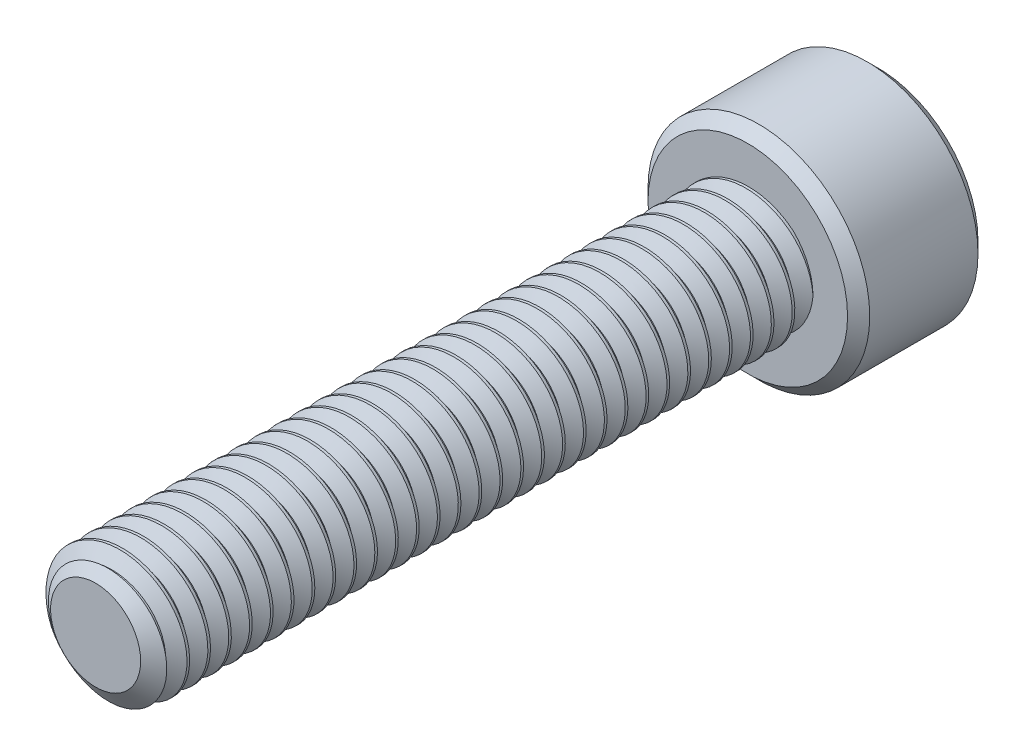
SolidWorks part; units mm, degrees
other "DetailItem1"
ref_plane "Front Plane" through (0, 0, 0) normal (0, 0, 1) x (1, 0, 0)
ref_plane "Top Plane" through (0, 0, 0) normal (0, 1, 0) x (1, 0, 0)
ref_plane "Right Plane" through (0, 0, 0) normal (1, 0, 0) x (0, 0, -1)
sketch "Sketch1" plane through (0, 0, 0) normal (0, 0, 1) x (1, 0, 0)
  circle A0 centre (0, 0) radius 2.5
  dimension "OD" = 5
extrude "Extrude1" add sketch "Sketch1" against normal blind 25
sketch "Sketch2" plane through (0, 0, 0) normal (0, 0, 1) x (1, 0, 0)
  circle A0 centre (0, 0) radius 2.5 construction
  circle A1 centre (0, 0) radius 2.5
curve "Helix/Spiral1" pitch 0.8 height 25.8 turns 32.25 parameters "pitch"=0.8
sketch "Sketch3" plane through (0, 0, 0) normal (1, 0, 0) x (0, 0, -1)
  line L0 (-0.7, 2.5) -> (-0.4, 1.9804)
  line L1 (-0.4, 1.9804) -> (-0.3, 1.9804)
  line L2 (-0.3, 1.9804) -> (0, 2.5)
  line L3 (-0.7, 2.5) -> (0, 2.5)
  line L4 (-0.35, 2.5) -> (-0.35, 1.9804) construction
  line L5 (-0.55, 2.2402) -> (-0.15, 2.2402) construction
  line L6 (0, 2.5) -> (0, -2.5) construction
  dimension "D1" = 0.1
  dimension "D2" = 0.4
  dimension "D3" = 60
sweep "Cut-Sweep1" cut profiles "Sketch3" path "Helix/Spiral1"
sketch "Sketch4" plane through (0, 0, 0) normal (1, 0, 0) x (0, 0, -1)
  line L0 (0.5417, 2.5) -> (0, 1.7264)
  line L1 (0, 1.7264) -> (0, 2.5)
  line L2 (0.5417, 2.5) -> (0, 2.5)
  line L3 (-0.7, 2.5) -> (0, 2.5) construction
  line L4 (0, 0) -> (7.0209, 0) construction
  dimension "D1" = 55
  dimension "D2" = 0.254
revolve "Cut-Revolve1" cut sketch "Sketch4" angle 360 about L4
sketch "Sketch6" plane through (0, 0, -25) normal (0, 0, -1) x (-1, 0, 0)
  circle A0 centre (0, 0) radius 4.25
  dimension "head dia" = 8.5
extrude "Extrude2" add sketch "Sketch6" along normal blind 5
sketch "Sketch7" plane through (0, 0, -30) normal (0, 0, -1) x (-1, 0, 0)
  line L1 (0, 2.3094) -> (-2, 1.1547)
  line L2 (-2, 1.1547) -> (-2, -1.1547)
  line L3 (-2, -1.1547) -> (0, -2.3094)
  line L4 (0, -2.3094) -> (2, -1.1547)
  line L5 (2, -1.1547) -> (2, 1.1547)
  line L6 (2, 1.1547) -> (0, 2.3094)
  circle A0 centre (0, 0) radius 2 construction
  dimension "hex dia" = 4
extrude "Cut-Extrude1" cut sketch "Sketch7" against normal blind 3
sketch "Sketch8" plane through (0, 0, -30) normal (0, 0, -1) x (-1, 0, 0)
  circle A0 centre (0, 0) radius 2.3094
extrude "Cut-Extrude2" cut sketch "Sketch8" against normal through all draft 45
chamfer "Chamfer1" distance 0.425 angle 45 2 edges at (-4.25, 0, -30) (-4.25, 0, -25)
sketch "Sketch10" plane through (0, 0, -25) normal (0, 0, 1) x (1, 0, 0)
  circle A1 centre (0, 0) radius 2.5
  circle A2 centre (0, 0) radius 2.5
  dimension "D1" = 0
ref_plane "Plane1" through (0, 0, 0) normal (0, 0, 1) x (1, 0, 0)
extrude "partial thread" [suppressed] add sketch "Sketch10" along normal up to surface (13 mm away) separate body
chamfer "Chamfer2" [suppressed] distance 0.1 angle 45
combine bodies "Combine1" [suppressed] operation type add bodies to combine 107 108
sketch "Sketch9" plane through (0, 0, 0) normal (1, 0, 0) x (0, 0, -1)
  line L0 (0, 2.5) -> (0, -2.5) construction
  line L1 (2, 2.5) -> (2, -2.5) construction
  dimension "D1" = 2
equation "\"D3@Helix/Spiral1\" = \"screw length@Extrude1\"+\"pitch@Helix/Spiral1\""
equation "\"D1@Sketch3\" = \"pitch@Helix/Spiral1\"*.125"
equation "\"D2@Sketch3\" = \"pitch@Helix/Spiral1\"*.5"
equation "\"D1@Cut-Extrude1\" = \"hex dia@Sketch7\"*.75"
equation "\"D1@Chamfer1\" = \"head dia@Sketch6\"*.05"
equation "\"D1@Sketch9\" = \"pitch@Helix/Spiral1\"*2.5"
equation "\"D1@Chamfer2\"=\"OD@Sketch1\"*.02"
